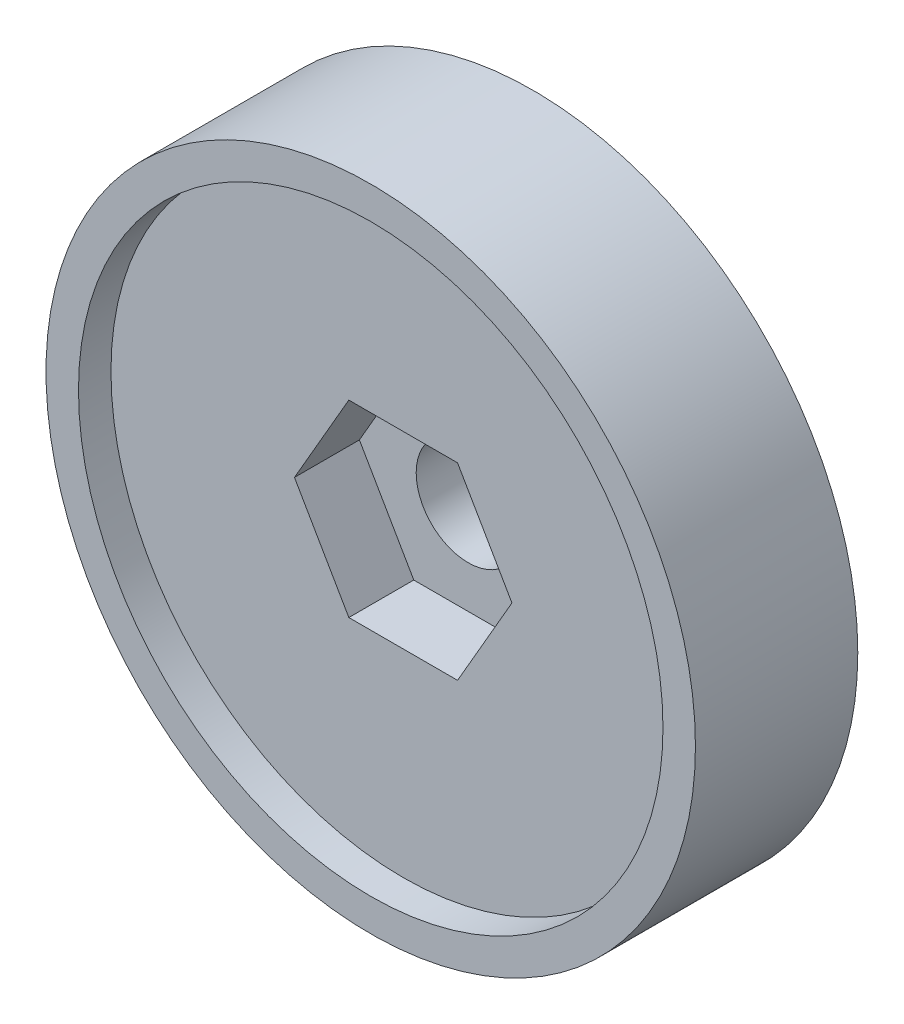
SolidWorks part; units mm, degrees
ref_plane "Front Plane" through (0, 0, 0) normal (0, 0, 1) x (1, 0, 0)
ref_plane "Top Plane" through (0, 0, 0) normal (0, 1, 0) x (1, 0, 0)
ref_plane "Right Plane" through (0, 0, 0) normal (1, 0, 0) x (0, 0, -1)
sketch "Sketch1" plane through (0, 0, 0) normal (0, 0, 1) x (1, 0, 0)
  circle A0 centre (-85, 80) radius 10
  circle A1 centre (-85, 80) radius 1.5 construction
  circle A2 centre (-85, 80) radius 1.5
  dimension "D1" = 20
extrude "Boss-Extrude1" add sketch "Sketch1" along normal blind 2
sketch "Sketch2" plane through (0, 0, 2) normal (0, 0, 1) x (1, 0, 0)
  circle A0 centre (-85, 80) radius 10
  circle A1 centre (-85, 80) radius 1.5 construction
  circle A2 centre (-85, 80) radius 1.5
  circle M3 centre (-85, 80) radius 1.5
  dimension "D1" = 20
extrude "Boss-Extrude2" add sketch "Sketch2" along normal blind 3 contours A0 M3 | M3 region at (-94.7172, 80, 2) region at (-85, 80, 2)
sketch "Sketch3" plane through (0, 0, 0) normal (0, 0, -1) x (-1, 0, 0)
  circle A0 centre (85, 80) radius 1.6
  dimension "D1" = 3.2
extrude "Cut-Extrude1" cut sketch "Sketch3" against normal through all
sketch "Sketch4" plane through (0, 0, 5) normal (0, 0, 1) x (1, 0, 0)
  line L1 (-88.3486, 80) -> (-86.6743, 77.1)
  line L2 (-86.6743, 77.1) -> (-83.3257, 77.1)
  line L3 (-83.3257, 77.1) -> (-81.6514, 80)
  line L4 (-81.6514, 80) -> (-83.3257, 82.9)
  line L5 (-83.3257, 82.9) -> (-86.6743, 82.9)
  line L6 (-86.6743, 82.9) -> (-88.3486, 80)
  circle A0 centre (-85, 80) radius 2.9 construction
  dimension "D1" = 5.8
extrude "Cut-Extrude2" cut sketch "Sketch4" against normal offset from surface (3 mm away) 2 up to face at (-86.6, 80, 0)
sketch "Sketch5" plane through (0, 0, 5) normal (0, 0, 1) x (1, 0, 0)
  circle A0 centre (-85, 80) radius 9
  circle A1 centre (-85, 80) radius 10 construction
  dimension "D1" = 18
extrude "Cut-Extrude3" cut sketch "Sketch5" against normal blind 1
